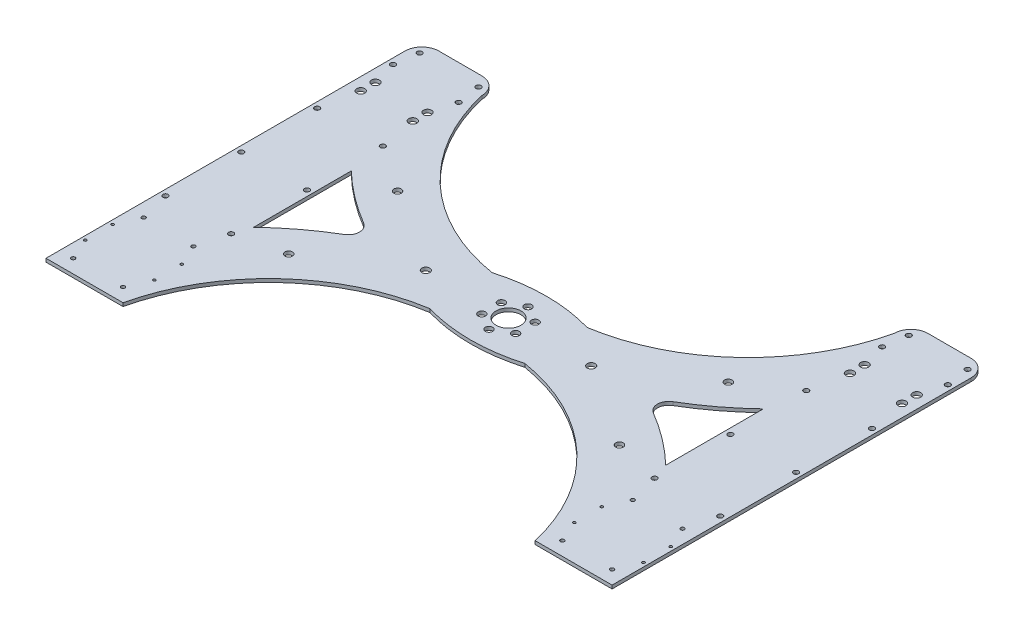
SolidWorks part; units mm, degrees
material "6061 Alloy"
ref_plane "Front Plane" through (0, 0, 0) normal (0, 0, 1) x (1, 0, 0)
ref_plane "Top Plane" through (0, 0, 0) normal (0, 1, 0) x (1, 0, 0)
ref_plane "Right Plane" through (0, 0, 0) normal (1, 0, 0) x (0, 0, -1)
sketch "Sketch1" plane through (0, 0, 0) normal (0, 1, 0) x (1, 0, 0)
  line L1 (-250, -158.5) -> (250, -158.5) construction
  line L2 (-250, -158.5) -> (-250, 158.5) construction
  line L3 (-250, 158.5) -> (250, 158.5) construction
  line L4 (250, -158.5) -> (250, 158.5) construction
  line L5 (-250, -158.5) -> (250, 158.5) construction
  line L6 (-250, 158.5) -> (250, -158.5) construction
  line L8 (0, 0) -> (0, -33.5) construction
  line L9 (0, 0) -> (250, 0) construction
  line L10 (0, 0) -> (0, 158.5) construction
  line L14 (0, 0) -> (-54.5, 0) construction
  line L22 (-54.5, 0) -> (-54.5, -34.553) construction
  line L23 (-197, -158.5) -> (-250, -158.5) construction
  line L24 (-41.906, 27.5) -> (41.906, 27.5) construction
  line L25 (0, 0) -> (-250, 0) construction
  circle A4 centre (39.6, 0) radius 6.35
  circle A5 centre (-39.6, 0) radius 6.35
  circle A6 centre (0, 0) radius 11
  arc A7 (-223.5, -158.5) -> (0, 0) centre (-10.6329, -221.8347) cw construction
  arc A9 (-41.906, -27.5) -> (-197, -158.5) centre (-10.6329, -221.8347) ccw
  arc A11 (-250, -158.5) -> (-197, -158.5) centre (-223.5, -158.5) ccw
  arc A12 (-223.5, 158.5) -> (0, 0) centre (-10.6329, 221.8347) ccw construction
  arc A14 (-41.906, 27.5) -> (-197, 158.5) centre (-10.6329, 221.8347) cw
  arc A16 (-250, 158.5) -> (-197, 158.5) centre (-223.5, 158.5) cw
  arc A17 (223.5, -158.5) -> (0, 0) centre (10.6329, -221.8347) ccw construction
  arc A19 (41.906, -27.5) -> (197, -158.5) centre (10.6329, -221.8347) cw
  arc A21 (250, -158.5) -> (197, -158.5) centre (223.5, -158.5) cw
  arc A22 (223.5, 158.5) -> (0, 0) centre (10.6329, 221.8347) cw construction
  arc A24 (41.906, 27.5) -> (197, 158.5) centre (10.6329, 221.8347) ccw
  arc A26 (250, 158.5) -> (197, 158.5) centre (223.5, 158.5) ccw
  arc A27 (-41.906, -27.5) -> (41.906, -27.5) centre (0, 115.8429) ccw
  arc A28 (-41.906, 27.5) -> (41.906, 27.5) centre (0, -115.8429) cw
  arc A29 (-136.5048, 8.6115) -> (-250, 158.5) centre (-10.6329, 221.8347) cw
  arc A30 (136.5048, 8.6115) -> (250, 158.5) centre (10.6329, 221.8347) ccw
  arc A31 (136.5048, -8.6115) -> (250, -158.5) centre (10.6329, -221.8347) cw
  arc A34 (-136.5048, -8.6115) -> (-250, -158.5) centre (-10.6329, -221.8347) ccw
  arc A35 (-136.5048, -8.6115) -> (-136.5048, 8.6115) centre (-141.5884, 0) ccw
  arc A36 (136.5048, 8.6115) -> (136.5048, -8.6115) centre (141.5884, 0) ccw
  point P0 (0, 0)
  point P6 (-197, -158.5)
  point P13 (-223.5, -158.5)
  point P15 (0, -33.5)
  point P33 (0, 33.5)
  point P61 (-120.6204, 0)
  point P65 (120.6204, 0)
  dimension "D6" = 26.5
  dimension "D9" = 12.7
  dimension "D10" = 22
  dimension "D7" = 83.812
  dimension "D15" = 10
  dimension "D16" = 10
  dimension "D1" = 317
  dimension "D2" = 500
  dimension "D3" = 33.5
  dimension "D4" = 54.5
  dimension "D5" = 53
  dimension "D8" = 39.6
  dimension "D11" = 55
  dimension "D12" = 53
  dimension "D13" = 53
  dimension "D14" = 53
extrude "Boss-Extrude1" add sketch "Sketch1" along normal blind 3
sketch "Sketch3" plane through (0, 3, 0) normal (0, 1, 0) x (1, 0, 0)
  line L1 (-250, 158.5) -> (265.5968, 158.5)
  line L2 (-250, 158.5) -> (-250, 200.3351)
  line L3 (-250, 200.3351) -> (265.5968, 200.3351)
  line L4 (265.5968, 158.5) -> (265.5968, 200.3351)
  line L5 (-250, -158.5) -> (265.5968, -158.5)
  line L6 (-250, -158.5) -> (-250, -198.288)
  line L7 (-250, -198.288) -> (265.5968, -198.288)
  line L8 (265.5968, -158.5) -> (265.5968, -198.288)
extrude "Cut-Extrude1" cut sketch "Sketch3" against normal blind 4
sketch "Sketch8" plane through (0, 0, 0) normal (0, -1, 0) x (1, 0, 0)
  line L0 (-250, -158.5) -> (-250, 158.5)
  line L1 (-197, -158.5) -> (-182, -158.5)
  line L2 (-182, -43.1137) -> (-182, 43.1137)
  line L3 (0, 0) -> (0, 106.2907) construction
  line L4 (250, -158.5) -> (250, 158.5)
  line L5 (182, -43.1137) -> (182, 43.1137)
  line L6 (0, 0) -> (182, 0) construction
  line L7 (-197, 158.5) -> (-182, 158.5)
  line L8 (197, 158.5) -> (182, 158.5)
  line L9 (197, -158.5) -> (182, -158.5)
  arc A0 (-136.5048, -8.6115) -> (-250, -158.5) centre (-10.6329, -221.8347) ccw construction
  arc A1 (-250, 158.5) -> (-136.5048, 8.6115) centre (-10.6329, 221.8347) ccw construction
  arc A2 (-250, -158.5) -> (-182, -43.1137) centre (-10.6329, -221.8347) cw
  arc A3 (-250, 158.5) -> (-182, 43.1137) centre (-10.6329, 221.8347) ccw
  arc A4 (250, -158.5) -> (182, -43.1137) centre (10.6329, -221.8347) ccw
  arc A5 (250, 158.5) -> (182, 43.1137) centre (10.6329, 221.8347) cw
  arc A6 (-182, -158.5) -> (-41.906, -27.5) centre (-14.6139, -197.0964) cw
  arc A7 (-41.906, -27.5) -> (41.906, -27.5) centre (0, 115.8429) ccw construction
  arc A8 (-182, 158.5) -> (-41.906, 27.5) centre (-14.6139, 197.0964) ccw
  arc A9 (-197, 158.5) -> (-41.906, 27.5) centre (-10.6329, 221.8347) ccw
  arc A10 (197, 158.5) -> (41.906, 27.5) centre (10.6329, 221.8347) cw
  arc A11 (182, 158.5) -> (41.906, 27.5) centre (14.6139, 197.0964) cw
  arc A12 (182, -158.5) -> (41.906, -27.5) centre (14.6139, -197.0964) ccw
  arc A13 (197, -158.5) -> (41.906, -27.5) centre (10.6329, -221.8347) ccw
  arc A14 (-41.906, -27.5) -> (-197, -158.5) centre (-10.6329, -221.8347) ccw construction
  arc A15 (-197, -158.5) -> (-41.906, -27.5) centre (-10.6329, -221.8347) cw
  dimension "D2" = 68
  dimension "D1" = 68
extrude "Boss-Extrude2" add sketch "Sketch8" against normal blind 3
sketch "Sketch11" plane through (0, 3, 0) normal (0, 1, 0) x (1, 0, 0)
  line L0 (250, 158.5) -> (250, 173.5)
  line L1 (250, 173.5) -> (184.7638, 173.5)
  line L2 (250, 158.5) -> (182, 158.5)
  line L3 (182, 158.5) -> (182, 173.5)
  line L4 (182, 173.5) -> (184.7638, 173.5)
  line L6 (0, -1.65) -> (0, 1.65) construction
  line L7 (-182, 173.5) -> (-184.7638, 173.5)
  line L8 (-182, 158.5) -> (-182, 173.5)
  line L9 (-250, 158.5) -> (-250, 173.5)
  line L10 (-250, 158.5) -> (-182, 158.5)
  line L11 (-250, 173.5) -> (-184.7638, 173.5)
  circle A0 centre (14.6139, 197.0964) radius 171.7783 construction
  arc A1 (182, 158.5) -> (184.7638, 173.5) centre (14.6139, 197.0964) ccw construction
  arc A2 (41.906, 27.5) -> (182, 158.5) centre (14.6139, 197.0964) ccw construction
  dimension "D1" = 15
extrude "Boss-Extrude3" add sketch "Sketch11" against normal up to vertex (3 mm away) contours L1 L4 L3 L2 L0 | L11 L7 L8 L10 L9 up to point (250, 0, -158.5)
fillet "Fillet3" radius 15 4 edges at (250, 1.5, -173.5) (182, 1.5, -173.5) (-182, 1.5, -173.5) (-250, 1.5, -173.5)
sketch "Sketch13" plane through (0, 3, 0) normal (0, 1, 0) x (1, 0, 0)
  line L4 (-182, -158.5) -> (-250, -158.5) construction
  line L5 (-250, -158.5) -> (-250, 158.5) construction
  line L6 (-235, 173.5) -> (-198.2437, 173.5) construction
  line L7 (-182, 158.5) -> (-182, -158.5) construction
  arc A19 (-250, 158.5) -> (-235, 173.5) centre (-235, 158.5) cw construction
  arc A20 (-198.2437, 173.5) -> (-182, 158.5) centre (-197.6218, 157.8782) cw construction
  circle A21 centre (-185.5, -127.3333) radius 1.2
  circle A22 centre (-185.5, -103.1667) radius 1.2
  circle A23 centre (-246.5, -103.1667) radius 1.2
  circle A24 centre (-246.5, -127.3333) radius 1.2
  circle A25 centre (-187, -58) radius 2.25
  circle A26 centre (-187, 9) radius 2.25
  circle A27 centre (-187, 76) radius 2.25
  circle A28 centre (-187, 143) radius 2.25
  circle A29 centre (-245, 143) radius 2.25
  circle A30 centre (-245, 76) radius 2.25
  circle A31 centre (-245, 9) radius 2.25
  circle A32 centre (-245, -58) radius 2.25
  circle A33 centre (-242, 163.5) radius 2.25
  circle A34 centre (-190, 163.5) radius 2.25
  point P36 (-250, -158.5)
  dimension "D1" = 4.5
  dimension "D2" = 2.4
extrude "Cut-Extrude2" cut sketch "Sketch13" against normal blind 10
sketch "Sketch14" plane through (0, 3, 0) normal (0, 1, 0) x (1, 0, 0)
  line L0 (-250, -158.5) -> (-182, -158.5) construction
  line L1 (-182, -158.5) -> (-182, 158.5) construction
  line L2 (-250, 158.5) -> (-250, -158.5) construction
  line L3 (-182, -158.5) -> (-250, -158.5) construction
  line L4 (-197, 173.5) -> (-235, 173.5) construction
  arc A0 (-182, 158.5) -> (-197, 173.5) centre (-197, 158.5) ccw construction
  arc A1 (-235, 173.5) -> (-250, 158.5) centre (-235, 158.5) ccw construction
  circle A2 centre (-194, -146.5) radius 1.7
  circle A3 centre (-238, -146.5) radius 1.7
  circle A4 centre (-194, -84.3) radius 1.7
  circle A5 centre (-238, -84.3) radius 1.7
  point P17 (-216, -158.5)
  dimension "D1" = 3.4
  dimension "D2" = 15
  dimension "D3" = 41
  dimension "D4" = 3
  dimension "D5" = 257.8
  dimension "D6" = 320
extrude "Cut-Extrude3" cut sketch "Sketch14" against normal blind 10
mirror "Mirror4" about plane through (0, 0, 0) normal (1, 0, 0) of "Cut-Extrude3", "Cut-Extrude2"
sketch "Sketch16" plane through (0, 3, 0) normal (0, 1, 0) x (1, 0, 0)
  circle A0 centre (-39.6, 0) radius 6.35
  circle A1 centre (39.6, 0) radius 6.35
extrude "Boss-Extrude5" add sketch "Sketch16" against normal up to surface (3 mm away) up to face at (238, 0, 148.2)
sketch "Sketch17" plane through (0, 3, 0) normal (0, 1, 0) x (1, 0, 0)
  circle A0 centre (0, 0) radius 27 construction
  circle A1 centre (0, 0) radius 19 construction
  circle A2 centre (0, 19) radius 2.5
  circle A3 centre (19, 0) radius 2.5
  circle A4 centre (0, -19) radius 2.5
  circle A5 centre (-19, 0) radius 2.5
  point P15 (0, 0)
  dimension "D1" = 54
  dimension "D2" = 38
  dimension "D3" = 5
  dimension "D4" = 4
extrude "Cut-Extrude4" cut sketch "Sketch17" against normal blind 10
sketch "Sketch18" plane through (0, 0, 0) normal (0, -1, 0) x (1, 0, 0)
  circle A0 centre (-39.6, 0) radius 6.35
  circle A1 centre (39.6, 0) radius 6.35
extrude "Boss-Extrude6" add sketch "Sketch18" against normal up to surface (3 mm away) up to face at (0, 3, -16.5)
sketch "Sketch19" plane through (0, 0, 0) normal (0, -1, 0) x (1, 0, 0)
  line L0 (-131.9389, 71.6267) -> (-160.2503, 24.5468) construction
  line L1 (1.65, 0) -> (-1.65, 0) construction
  line L2 (-131.9389, -71.6267) -> (-160.2503, -24.5468) construction
  line L3 (0, -1.65) -> (0, 1.65) construction
  line L4 (131.9389, -71.6267) -> (160.2503, -24.5468) construction
  line L5 (131.9389, 71.6267) -> (160.2503, 24.5468) construction
  arc A3 (-182, 43.1137) -> (-136.5048, 8.6115) centre (-10.6329, 221.8347) ccw construction
  arc A4 (-182, 158.5) -> (-41.906, 27.5) centre (-14.6139, 197.0964) ccw construction
  circle A5 centre (-146.0946, 48.0867) radius 3.3
  circle A6 centre (146.0946, 48.0867) radius 3.3
  circle A7 centre (146.0946, -48.0867) radius 3.3
  circle A8 centre (-146.0946, -48.0867) radius 3.3
  dimension "D1" = 6.6
  dimension "D2" = 6.6
  dimension "D3" = 6.6
  dimension "D4" = 6.6
extrude "Cut-Extrude5" cut sketch "Sketch19" against normal blind 10
sketch "Sketch20" plane through (0, 0, 0) normal (0, -1, 0) x (1, 0, 0)
  line L0 (-235, -173.5) -> (-197, -173.5) construction
  line L1 (-182, -158.5) -> (-182, -81.6683) construction
  line L2 (-250, -158.5) -> (-250, -81.6683) construction
  line L3 (-250, -81.6683) -> (-182, -81.6683) construction
  arc A0 (-250, -158.5) -> (-235, -173.5) centre (-235, -158.5) ccw construction
  arc A1 (-197, -173.5) -> (-182, -158.5) centre (-197, -158.5) ccw construction
  circle A2 centre (-239.0421, -108.5011) radius 3.55
  circle A3 centre (-239.0421, -121.5011) radius 3.55
  circle A4 centre (-193.0421, -108.5011) radius 3.55
  circle A5 centre (-193.0421, -121.5011) radius 3.55
  dimension "D1" = 7.1
  dimension "D2" = 7.1
  dimension "D3" = 7.1
  dimension "D4" = 7.1
  dimension "D5" = 15
  dimension "D6" = 51.9989
  dimension "D7" = 10.9579
  dimension "D9" = 46
  dimension "D8" = 13
extrude "Cut-Extrude6" cut sketch "Sketch20" against normal blind 50
mirror "Mirror5" about plane through (0, 0, 0) normal (1, 0, 0) of "Cut-Extrude6"
sketch "Sketch21" plane through (0, 0, 0) normal (0, -1, 0) x (1, 0, 0)
  line L0 (-73.0496, 35.5629) -> (-73.0496, -35.5629) construction
  line L1 (-146.0946, -48.0867) -> (0, -19) construction
  arc A0 (-182, 158.5) -> (-41.906, 27.5) centre (-14.6139, 197.0964) ccw construction
  arc A1 (-41.906, -27.5) -> (-182, -158.5) centre (-14.6139, -197.0964) ccw construction
  circle A2 centre (-146.0946, -48.0867) radius 3.3 construction
  circle A3 centre (-73.0496, 0) radius 3.5
  dimension "D3" = 7
  dimension "D1" = 146.0946
  dimension "D2" = 73.045
extrude "Cut-Extrude7" cut sketch "Sketch21" against normal blind 50
mirror "Mirror6" about plane through (0, 0, 0) normal (1, 0, 0) of "Cut-Extrude7"
sketch "Sketch22" plane through (0, 0, 0) normal (0, -1, 0) x (1, 0, 0)
  circle A0 centre (0, -19) radius 2.5
  circle A3 centre (0, -19) radius 2.5 construction
  circle A4 centre (-19, 0) radius 2.5
  circle A5 centre (0, 19) radius 2.5
  circle A6 centre (19, 0) radius 2.5
  circle A7 centre (0, 0) radius 19 construction
  point P14 (0, 0)
  dimension "D1" = 4
extrude "Boss-Extrude7" add sketch "Sketch22" against normal up to surface (3 mm away) up to face at (73.0496, 3, 3.5)
sketch "Sketch23" plane through (0, 0, 0) normal (0, -1, 0) x (1, 0, 0)
  circle A0 centre (0, 0) radius 17.25 construction
  circle A1 centre (0, 17.25) radius 3.25
  circle A2 centre (14.9389, 8.625) radius 3.25
  circle A3 centre (14.9389, -8.625) radius 3.25
  circle A4 centre (0, -17.25) radius 3.25
  circle A5 centre (-14.9389, -8.625) radius 3.25
  circle A6 centre (-14.9389, 8.625) radius 3.25
  point P17 (0, 0)
  dimension "D1" = 34.5
  dimension "D2" = 6.5
  dimension "D3" = 6
extrude "Cut-Extrude8" cut sketch "Sketch23" against normal up to surface (3 mm away) up to face at (73.0496, 3, 3.5)
